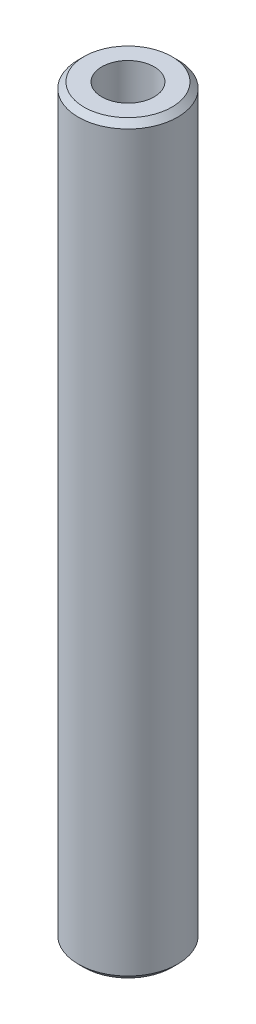
SolidWorks part; units mm, degrees
ref_plane "Front Plane" through (0, 0, 0) normal (0, 0, 1) x (1, 0, 0)
ref_plane "Top Plane" through (0, 0, 0) normal (0, 1, 0) x (1, 0, 0)
ref_plane "Right Plane" through (0, 0, 0) normal (1, 0, 0) x (0, 0, -1)
sketch "Sketch1" plane through (0, 0, 0) normal (0, 1, 0) x (1, 0, 0)
  circle A0 centre (0, 0) radius 40
  dimension "SHAFT_OD" = 80
extrude "Boss-Extrude1" add sketch "Sketch1" along normal blind 600
sketch "Sketch2" plane through (0, 0, 0) normal (0, 1, 0) x (1, 0, 0)
  circle A0 centre (0, 0) radius 21.0634
  dimension "BORE_D" = 42.1269
extrude "Cut-Extrude1" cut sketch "Sketch2" along normal through all
chamfer "Chamfer1" distance 4.6603 angle 45 2 edges at (0, 600, 40) (0, 0, 40)
